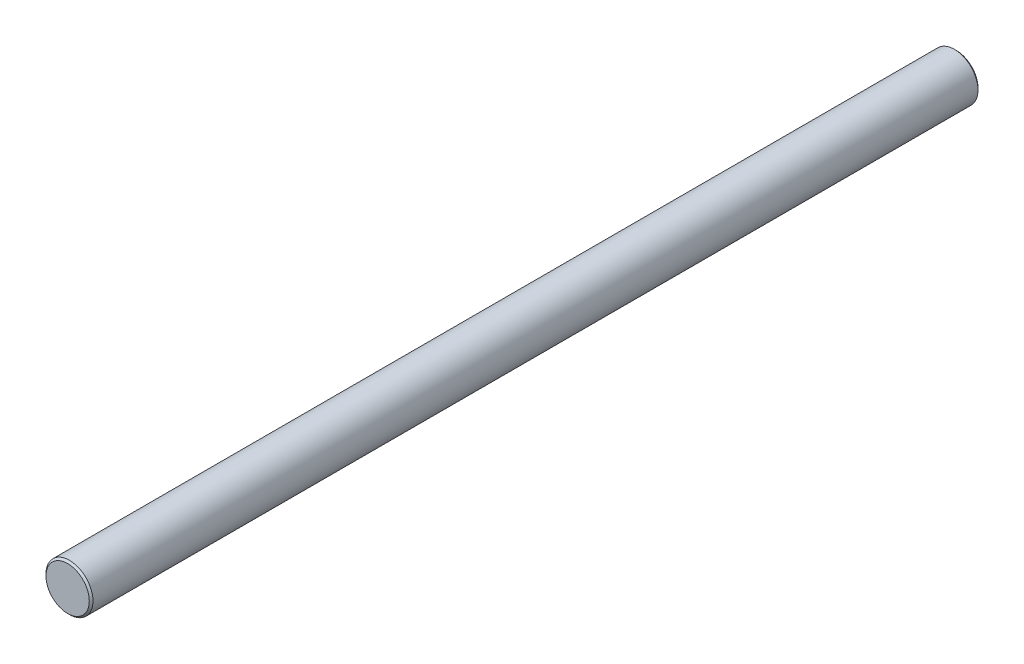
SolidWorks part; units mm, degrees
material "Plain Carbon Steel"
ref_plane "Front Plane" through (0, 0, 0) normal (0, 0, 1) x (1, 0, 0)
ref_plane "Top Plane" through (0, 0, 0) normal (0, 1, 0) x (1, 0, 0)
ref_plane "Right Plane" through (0, 0, 0) normal (1, 0, 0) x (0, 0, -1)
sketch "Sketch1" plane through (0, 0, 0) normal (0, 0, 1) x (1, 0, 0)
  circle A0 centre (0, 0) radius 6.35
  dimension "D1" = 12.7
extrude "Boss-Extrude1" add sketch "Sketch1" along normal blind 240
chamfer "Chamfer1" distance 0.5 angle 45 2 edges at (6.35, 0, 0) (6.35, 0, 240)
